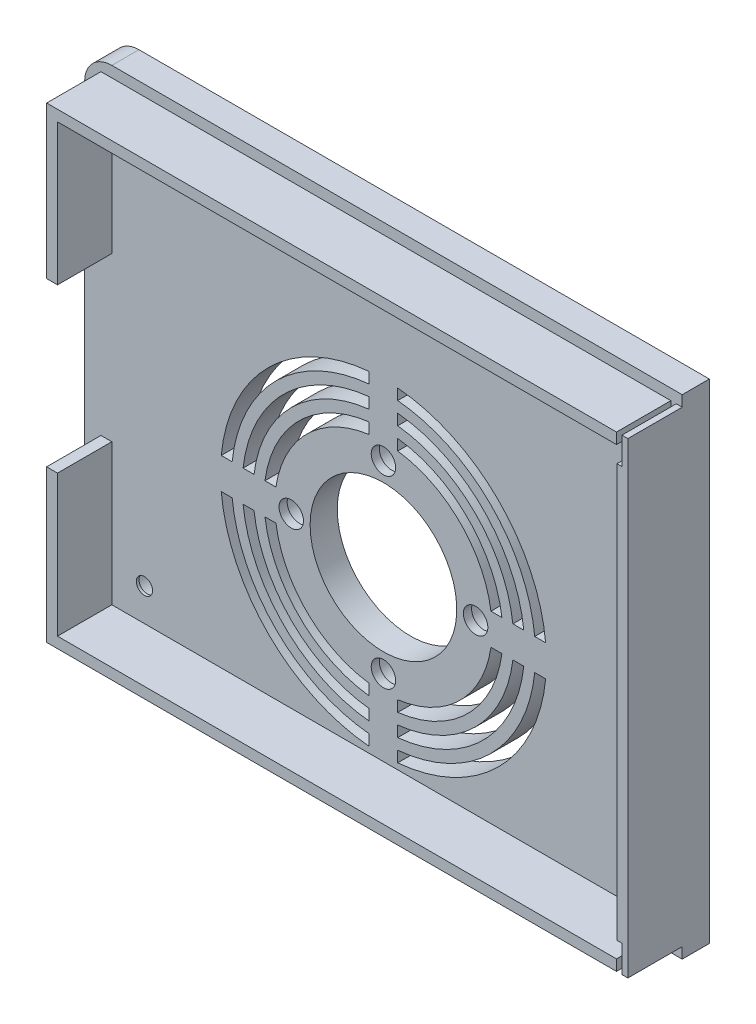
SolidWorks part; units mm, degrees
material "ABS"
ref_plane "Front Plane" through (0, 0, 0) normal (0, 0, 1) x (1, 0, 0)
ref_plane "Top Plane" through (0, 0, 0) normal (0, 1, 0) x (1, 0, 0)
ref_plane "Right Plane" through (0, 0, 0) normal (1, 0, 0) x (0, 0, -1)
sketch "Sketch1" plane through (0, 0, 0) normal (0, 0, 1) x (1, 0, 0)
  line L1 (55, 45) -> (-55, 45)
  line L2 (55, 45) -> (55, -45)
  line L3 (55, -45) -> (-55, -45)
  line L4 (-55, 45) -> (-55, -45)
  line L5 (0, -45) -> (0, 45) construction
  line L6 (55, 0) -> (-55, 0) construction
  point P0 (0, 0)
  dimension "D1" = 110
  dimension "D2" = 90
extrude "Boss-Extrude1" add sketch "Sketch1" along normal blind 5
sketch "Sketch3" plane through (0, 0, 5) normal (0, 0, 1) x (1, 0, 0)
  line L0 (0, 34) -> (0, -34)
  line L1 (-34, 0) -> (34, 0)
  circle A10 centre (0, 0) radius 34
  circle A11 centre (0, 0) radius 30
  circle A12 centre (0, 0) radius 24
  circle A13 centre (0, 0) radius 18
  circle A14 centre (0, 0) radius 14
  circle A15 centre (0, 0) radius 10
  circle A16 centre (0, 0) radius 12
  circle A17 centre (0, 0) radius 16
  circle A18 centre (0, 0) radius 20
  circle A19 centre (0, 0) radius 22
  circle A20 centre (0, 0) radius 26
  circle A21 centre (0, 0) radius 28
  circle A22 centre (0, 0) radius 32
  circle A23 centre (0, 0) radius 8
  circle A24 centre (0, 0) radius 6
  circle A25 centre (0, 0) radius 4
  circle A26 centre (0, 0) radius 2
  dimension "D1" = 68
  dimension "D2" = 64
  dimension "D3" = 60
  dimension "D4" = 56
  dimension "D5" = 52
  dimension "D6" = 48
  dimension "D7" = 44
  dimension "D8" = 40
  dimension "D9" = 36
  dimension "D10" = 32
  dimension "D11" = 28
  dimension "D12" = 24
  dimension "D13" = 20
  dimension "D14" = 16
  dimension "D15" = 12
  dimension "D16" = 8
  dimension "D17" = 4
sketch "Sketch6" plane through (0, 0, 5) normal (0, 0, 1) x (1, 0, 0)
  line L0 (55, -45) -> (55, 45) construction
  line L1 (55, 41) -> (-50, 41)
  line L2 (55, 41) -> (55, -41)
  line L3 (55, -41) -> (-50, -41)
  line L8 (-50, 41) -> (-50, -41)
  line L9 (55, 45) -> (-55, 45) construction
  line L10 (-55, -45) -> (55, -45) construction
  circle A0 centre (-44, 35) radius 1.5
  circle A1 centre (-44, -35) radius 1.5
  dimension "D1" = 3
  dimension "D2" = 3
  dimension "D4" = 82
  dimension "D5" = 4
  dimension "D6" = 4
  dimension "D3" = 105
  dimension "D8" = 6
  dimension "D9" = 6
  dimension "D10" = 6
  dimension "D7" = 6
extrude "Cut-Extrude5" cut sketch "Sketch6" against normal up to next contours A0 | A1
sketch "Sketch7" plane through (0, 0, 0) normal (0, 0, -1) x (-1, 0, 0)
  circle A0 centre (44, 35) radius 3
  circle A1 centre (44, -35) radius 3
  dimension "D1" = 6
  dimension "D2" = 6
extrude "Cut-Extrude6" cut sketch "Sketch7" against normal blind 3
fillet "Fillet2" radius 5 2 edges at (-55, 45, 2.5) (-55, -45, 2.5)
sketch "Sketch12" plane through (0, 0, 5) normal (0, 0, 1) x (1, 0, 0)
  line L0 (-55, 0) -> (55, 0) construction
  line L1 (55, -45) -> (-50, -45)
  line L2 (55, -45) -> (55, 45)
  line L3 (55, 45) -> (-50, 45)
  line L4 (-55, -40) -> (-55, 40)
  line L5 (2.5, 45) -> (2.5, -45) construction
  line L6 (-55, 15) -> (-52, 15)
  line L7 (55, 43) -> (-52, 43)
  line L8 (55, 43) -> (55, -43)
  line L9 (55, -43) -> (-52, -43)
  line L10 (-52, 43) -> (-52, -43)
  line L11 (1.5, -43) -> (1.5, 43) construction
  line L12 (55, 0) -> (-52, 0) construction
  line L13 (-55, -15) -> (-52, -15)
  line L14 (54, 41) -> (54, -41)
  line L15 (55, 41) -> (-50, 41)
  line L16 (55, 41) -> (55, -41)
  line L17 (55, -41) -> (-50, -41)
  line L18 (-50, 41) -> (-50, -41)
  line L19 (-55, 15) -> (-50, 15)
  line L20 (-55, 15) -> (-55, -15)
  line L21 (-55, -15) -> (-50, -15)
  line L22 (-50, 15) -> (-50, -15)
  line L23 (55, 41) -> (53, 41)
  line L24 (55, 41) -> (55, -41)
  line L25 (55, -41) -> (53, -41)
  line L26 (53, 41) -> (53, -41)
  arc A0 (-50, -45) -> (-55, -40) centre (-50, -40) cw
  arc A1 (-50, 45) -> (-55, 40) centre (-50, 40) ccw
  point P8 (1.5, 0)
  point P20 (-55, 45)
  dimension "D7" = 5
  dimension "D1" = 90
  dimension "D2" = 110
  dimension "D3" = 107
  dimension "D4" = 86
  dimension "D5" = 15
  dimension "D6" = 15
  dimension "D8" = 82
  dimension "D9" = 4
  dimension "D10" = 2
  dimension "D11" = 2
  dimension "D12" = 30
  dimension "D13" = 2
  dimension "D14" = 1
extrude "Boss-Extrude2" add sketch "Sketch12" along normal blind 10 contours L21 L10 L9 L2 L17 L18 | L10 L19 L18 L15 L8 L7 | L15 L26 L17 L14 | L17 L8 L15 L14 region at (1.5, -41.894, 5) region at (54.5, 0, 5) region at (54.5, 42.106, 5) region at (53.5, 0, 5)
chamfer "Chamfer1" distance 1.5 angle 60 1 edges at (-45.5, 35, 3) first distance on face at (-42.5, 35, 5)
chamfer "Chamfer2" distance 1.5 angle 60 1 edges at (-45.5, -35, 3) first distance on face at (-42.5, -35, 5)
sketch "Sketch14" plane through (0, 0, 0) normal (0, 0, -1) x (-1, 0, 0)
  line L0 (50, -45) -> (-55, -45) construction
  circle A0 centre (0, -10) radius 16.97
  circle A1 centre (0, 6.97) radius 2.25
  circle A2 centre (16.97, -10) radius 2.25
  circle A3 centre (0, -26.97) radius 2.25
  circle A4 centre (-16.97, -10) radius 2.25
  dimension "D1" = 33.94
  dimension "D2" = 4.5
  dimension "D3" = 33.94
  dimension "D4" = 35
extrude "Cut-Extrude7" cut sketch "Sketch14" against normal up to next contours A1 | A2 | A3 | A4
sketch "Sketch15" plane through (0, 0, 0) normal (0, 0, -1) x (-1, 0, 0)
  circle A0 centre (0, 6.97) radius 3
  circle A1 centre (0, -26.97) radius 3
  circle A2 centre (-16.97, -10) radius 3
  circle A3 centre (16.97, -10) radius 3
  dimension "D1" = 6
extrude "Cut-Extrude8" cut sketch "Sketch15" against normal blind 3.5
sketch "Sketch16" plane through (0, 0, 5) normal (0, 0, 1) x (1, 0, 0)
  line L1 (-50, 41) -> (53, 41)
  line L2 (-50, 41) -> (-50, -41)
  line L3 (-50, -41) -> (53, -41)
  line L4 (53, 41) -> (53, -41)
  line L5 (2.6259, 19.8849) -> (-2.6241, 19.8849)
  line L6 (2.6259, 19.8849) -> (2.6259, -39.885)
  line L7 (2.6259, -39.885) -> (-2.6241, -39.885)
  line L8 (-2.6241, 19.8849) -> (-2.6241, -39.885)
  line L9 (0.0009, -39.885) -> (0.0009, 19.8849) construction
  line L10 (2.6259, -10.0001) -> (-2.6241, -10.0001) construction
  line L12 (30, -7.142) -> (30, -12.858)
  line L14 (-30, -7.1591) -> (-30, -12.8751)
  line L15 (0.0009, -12.8751) -> (0.0009, -7.142) construction
  line L16 (30.0017, -7.1251) -> (-30, -7.1251)
  line L17 (30.0017, -7.1251) -> (30.0017, -12.8751)
  line L18 (30.0017, -12.8751) -> (-30, -12.8751)
  line L19 (-30, -7.1251) -> (-30, -12.8751)
  line L20 (0.0009, -12.8751) -> (0.0009, -7.1251) construction
  line L21 (30.0017, -10.0001) -> (-30, -10.0001) construction
  circle A0 centre (0.0009, -10.0001) radius 8.075
  circle A1 centre (0.0009, -10.0001) radius 12.5
  circle A2 centre (0.0009, -10.0001) radius 20
  circle A3 centre (0.0009, -10.0001) radius 22
  circle A4 centre (0.0009, -10.0001) radius 24
  circle A5 centre (0.0009, -10.0001) radius 26
  circle A6 centre (0.0009, -10.0001) radius 28
  circle A7 centre (0.0009, -10.0001) radius 30
  dimension "D1" = 16.15
  dimension "D2" = 25
  dimension "D3" = 40
  dimension "D4" = 44
  dimension "D5" = 48
  dimension "D6" = 52
  dimension "D7" = 56
  dimension "D8" = 60
  dimension "D9" = 5.25
  dimension "D10" = 5.75
extrude "Cut-Extrude9" cut sketch "Sketch16" against normal blind 40.5 contours L16 A1 L6 A0 | L18 A1 L16 A0 | L18 A1 L8 A0 | L16 A1 L18 A0 | L8 A1 L16 A0 | L8 A3 L16 A2 | L8 A5 L16 A4 | L8 A7 L16 A6 | L16 A3 L6 A2 | L16 A5 L6 A4 | L16 A7 L6 A6 | L6 A3 L18 A2 | L6 A5 L18 A4 | L6 A7 L18 A6 | L18 A7 L8 A6 | L18 A5 L8 A4 | L18 A3 L8 A2 | L6 A1 L18 A0 | L8 A0 L16 | L16 A0 L18 L8 | L18 A0 L8 | L6 A0 L18 | L16 A0 L6 | L18 A0 L16 L6 | L6 A1 L8 A0 | L6 A0 L8 L16 | L8 A0 L6 L18 | L8 A1 L6 A0 | L18 L6 L16 L8 region at (20.855, 11.0293, 5) region at (-3.0077, 18.8807, 5) region at (18.0666, 8.2412, 5) region at (-2.9509, 14.8615, 5) region at (-28.8561, -13.2587, 5) region at (15.2782, 5.4532, 5) region at (28.8578, -13.2587, 5) region at (-2.8939, 10.8348, 5) region at (-24.833, -13.2018, 5) region at (18.0666, -28.2414, 5) region at (7.0261, -2.7995, 5) region at (0.0009, 0.1678, 5) region at (-7.0243, -2.7995, 5) region at (-20.8009, -13.1449, 5) region at (4.5043, -5.3042, 5) region at (0.0009, -4.5957, 5) region at (10.1442, -10.0001, 5) region at (15.2782, -25.4534, 5) region at (-4.5026, -5.3042, 5) region at (-10.1424, -10.0001, 5) region at (5.2662, -10.0001, 5) region at (0.0009, -10.0001, 5) region at (-5.2645, -10.0001, 5) region at (-7.0243, -17.2007, 5) region at (4.5043, -14.6959, 5) region at (0.0009, -15.4045, 5) region at (7.0261, -17.2007, 5) region at (-4.5026, -14.6959, 5) region at (0.0009, -20.1679, 5)
sketch "Sketch17" plane through (0, 0, 0) normal (0, 0, -1) x (-1, 0, 0)
  circle A0 centre (-0.0009, -10.0001) radius 13.5
  dimension "D1" = 27
extrude "Cut-Extrude10" cut sketch "Sketch17" against normal up to next
sketch "Sketch18" plane through (0, 0, 15) normal (0, 0, 1) x (1, 0, 0)
  line L0 (55, -43) -> (-52, -43) construction
  line L1 (52.9089, -43) -> (53.9089, -43)
  line L2 (52.9089, -43) -> (52.9089, -38)
  line L3 (52.9089, -38) -> (53.9089, -38)
  line L4 (53.9089, -43) -> (53.9089, -38)
  line L5 (0, 0) -> (69.3311, 0) construction
  line L6 (52.9089, 43) -> (53.9089, 43)
  line L7 (52.9089, 38) -> (53.9089, 38)
  line L8 (53.9089, 43) -> (53.9089, 38)
  line L9 (52.9089, 43) -> (52.9089, 38)
  dimension "D1" = 5
  dimension "D2" = 1
extrude "Cut-Extrude11" cut sketch "Sketch18" against normal blind 10
